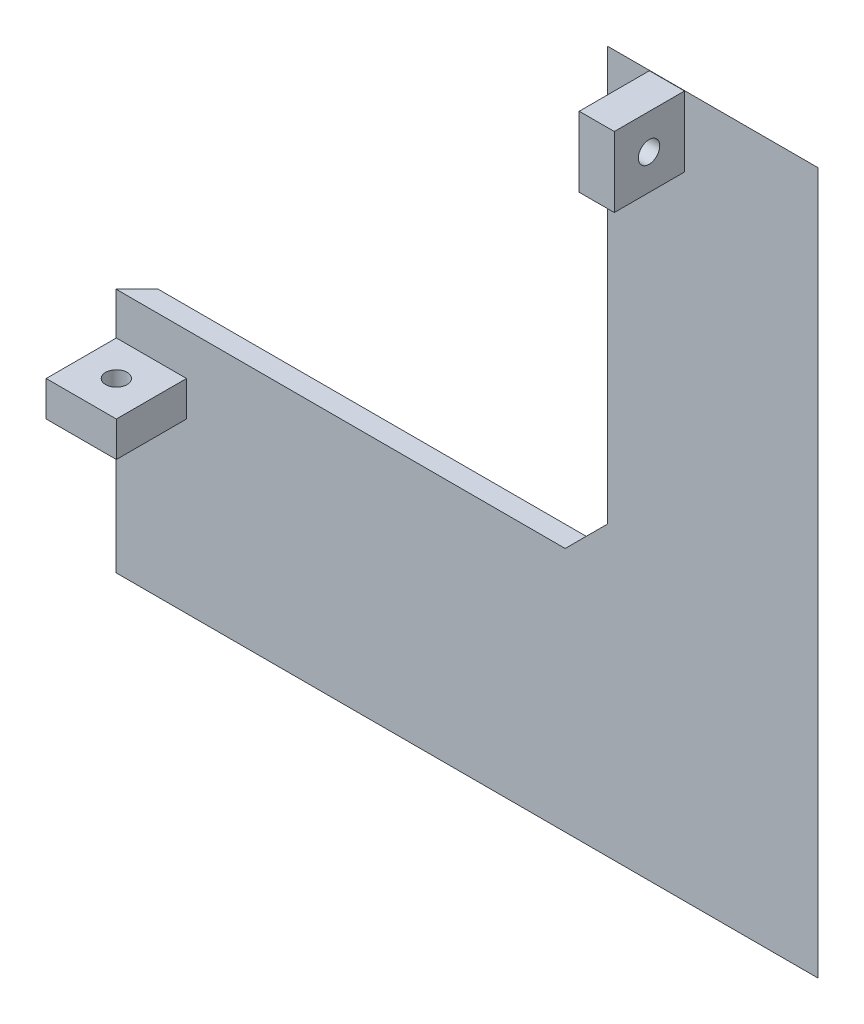
SolidWorks part; units mm, degrees
ref_plane "Plan de face" through (0, 0, 0) normal (0, 0, 1) x (1, 0, 0)
ref_plane "Plan de dessus" through (0, 0, 0) normal (0, 1, 0) x (1, 0, 0)
ref_plane "Plan de droite" through (0, 0, 0) normal (1, 0, 0) x (0, 0, -1)
sketch "Esquisse1" plane through (0, 0, 0) normal (0, 0, 1) x (1, 0, 0)
  line L1 (0, 100) -> (100, 100)
  line L2 (0, 100) -> (0, 0)
  line L3 (0, 0) -> (100, 0)
  line L4 (100, 100) -> (100, 0)
  dimension "D1" = 100
  dimension "D2" = 100
extrude "Boss.-Extru.1" add sketch "Esquisse1" along normal blind 3
chamfer "Chanfrein2" distance 3 angle 45 4 edges at (50, 0, 0) (100, 50, 0) (50, 100, 0) (0, 50, 0)
sketch "Esquisse4" plane through (0, 0, 3) normal (0, 0, 1) x (1, 0, 0)
  line L0 (100, 100) -> (0, 100) construction
  line L1 (81, 99.95) -> (76, 99.95)
  line L2 (81, 99.95) -> (81, 89.95)
  line L3 (81, 89.95) -> (76, 89.95)
  line L4 (76, 99.95) -> (76, 89.95)
  line L6 (0, 100) -> (0, 0) construction
  line L7 (10.05, 24) -> (0.05, 24)
  line L8 (10.05, 24) -> (10.05, 29)
  line L9 (10.05, 29) -> (0.05, 29)
  line L10 (0.05, 24) -> (0.05, 29)
  line L11 (0, 0) -> (100, 0) construction
  line L12 (100, 0) -> (100, 100) construction
  dimension "D1" = 5
  dimension "D2" = 10
  dimension "D3" = 0.05
  dimension "D4" = 19
  dimension "D5" = 5
  dimension "D6" = 10
  dimension "D7" = 0.05
  dimension "D8" = 24
extrude "Boss.-Extru.3" add sketch "Esquisse4" along normal blind 10
sketch "Esquisse5" plane through (81, 0, 0) normal (1, 0, 0) x (0, 0, -1)
  line L0 (-3, 89.95) -> (-3, 99.95) construction
  line L1 (-13, 99.95) -> (-3, 99.95) construction
  circle A0 centre (-8.05, 94.95) radius 1.525
  dimension "D1" = 3.05
  dimension "D2" = 5.05
  dimension "D3" = 5
extrude "Enlèv. mat.-Extru.2" cut sketch "Esquisse5" against normal blind 10 contours A0
sketch "Esquisse6" plane through (0, 29, 0) normal (0, 1, 0) x (1, 0, 0)
  line L0 (10.05, -3) -> (0.05, -3) construction
  line L1 (0.05, -13) -> (0.05, -3) construction
  circle A0 centre (5.05, -8) radius 1.525
  dimension "D1" = 3.05
  dimension "D2" = 5
  dimension "D3" = 5
extrude "Enlèv. mat.-Extru.3" cut sketch "Esquisse6" against normal blind 10
sketch "Esquisse7" plane through (0, 0, 3) normal (0, 0, 1) x (1, 0, 0)
  line L0 (0, 100) -> (0, 0) construction
  line L1 (0, 35) -> (70, 35)
  line L2 (0, 35) -> (0, 100)
  line L3 (0, 100) -> (70, 100)
  line L4 (70, 35) -> (70, 100)
  line L5 (100, 100) -> (0, 100) construction
  line L8 (100, 0) -> (100, 100) construction
  line L10 (0, 0) -> (100, 0) construction
  dimension "D1" = 30
  dimension "D2" = 35
extrude "Enlèv. mat.-Extru.4" cut sketch "Esquisse7" against normal blind 10
chamfer "Chanfrein3" distance 6 angle 45 1 edges at (70, 35, 1.5)
